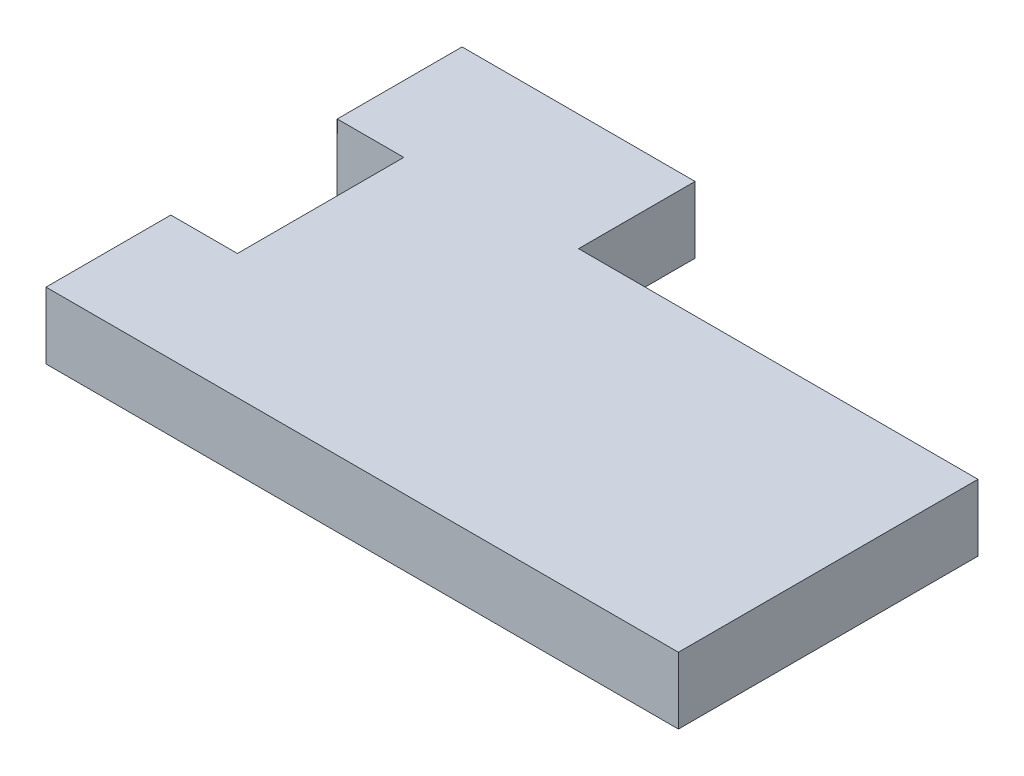
SolidWorks part; units mm, degrees
material "Maple"
ref_plane "Front Plane" through (0, 0, 0) normal (0, 0, 1) x (1, 0, 0)
ref_plane "Top Plane" through (0, 0, 0) normal (0, 1, 0) x (1, 0, 0)
ref_plane "Right Plane" through (0, 0, 0) normal (1, 0, 0) x (0, 0, -1)
sketch "Sketch1" plane through (0, 0, 0) normal (0, 1, 0) x (1, 0, 0)
  line L1 (0, 0) -> (38, 0)
  line L2 (0, 0) -> (0, -25)
  line L3 (0, -25) -> (38, -25)
  line L4 (38, 0) -> (38, -25)
  dimension "D1" = 38
  dimension "D2" = 25
extrude "Boss-Extrude1" add sketch "Sketch1" along normal blind 4
sketch "Sketch2" plane through (0, 4, 0) normal (0, 1, 0) x (1, 0, 0)
  line L0 (38, 0) -> (0, 0) construction
  line L1 (38, 0) -> (14, 0)
  line L2 (38, 0) -> (38, -7)
  line L3 (38, -7) -> (14, -7)
  line L4 (14, 0) -> (14, -7)
  line L5 (38, -25) -> (38, 0) construction
  dimension "D1" = 7
  dimension "D2" = 24
extrude "Cut-Extrude1" cut sketch "Sketch2" against normal through all
sketch "Sketch3" plane through (0, 0, 0) normal (0, -1, 0) x (1, 0, 0)
  line L0 (0, 0) -> (0, 25) construction
  line L1 (4, 7.5) -> (0, 7.5)
  line L2 (4, 7.5) -> (4, 17.5)
  line L3 (4, 17.5) -> (0, 17.5)
  line L4 (0, 7.5) -> (0, 17.5)
extrude "Cut-Extrude2" cut sketch "Sketch3" against normal through all
